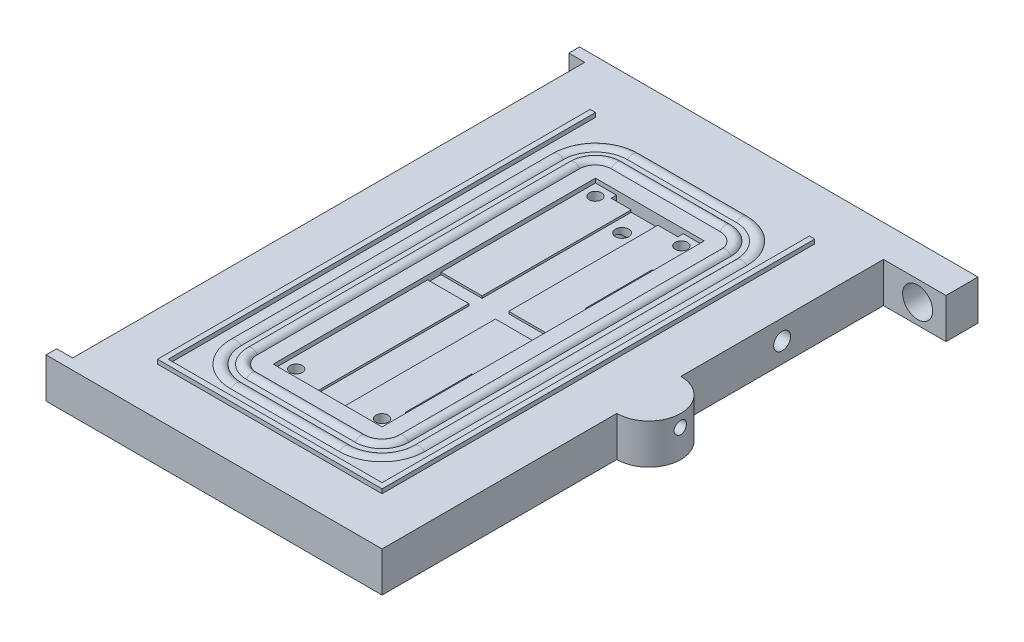
SolidWorks part; units mm, degrees
ref_plane "Front Plane" through (0, 0, 0) normal (0, 0, 1) x (1, 0, 0)
ref_plane "Top Plane" through (0, 0, 0) normal (0, 1, 0) x (1, 0, 0)
ref_plane "Right Plane" through (0, 0, 0) normal (1, 0, 0) x (0, 0, -1)
sketch "Sketch1" plane through (0, 0, 0) normal (0, 1, 0) x (1, 0, 0)
  line L12 (71.4455, 53.0596) -> (71.4455, -73.9404)
  line L13 (71.4455, -73.9404) -> (147.6455, -73.9404)
  line L14 (147.6455, -73.9404) -> (147.6455, 53.0596)
  line L15 (147.6455, 53.0596) -> (71.4455, 53.0596)
  dimension "D1" = 76.2
  dimension "D2" = 127
extrude "main body" add sketch "Sketch1" along normal blind 9.525
sketch "Sketch2" plane through (0, 9.525, 0) normal (0, 1, 0) x (1, 0, 0)
  line L0 (109.5455, 53.0596) -> (109.5455, 24.7212) construction
  line L1 (147.6455, 53.0596) -> (71.4455, 53.0596) construction
  line L2 (71.4455, -10.4404) -> (118.1145, -10.4404) construction
  line L3 (71.4455, 53.0596) -> (71.4455, -73.9404) construction
  line L4 (122.4995, -48.7944) -> (96.5915, -48.7944)
  line L5 (96.5915, -48.7944) -> (96.5915, 27.9136)
  line L6 (122.4995, -48.7944) -> (122.4995, 27.9136)
  line L7 (122.4995, 27.9136) -> (96.5915, 27.9136)
  line L8 (96.5915, 27.9136) -> (122.4995, -48.7944) construction
  point P11 (109.5455, 27.9136)
  point P13 (109.5455, -48.7944)
  point P14 (122.4995, -10.4404)
  point P15 (96.5915, -10.4404)
  dimension "D1" = 25.908
  dimension "D2" = 76.708
extrude "slide inset" cut sketch "Sketch2" against normal blind 1.016
ref_point "Point2 center of slide"
sketch "offset rounded from slide" plane through (0, 9.525, 0) normal (0, 1, 0) x (1, 0, 0)
  line L8 (125.0395, -51.3344) -> (125.0395, 30.4536)
  line L9 (94.0515, -51.3344) -> (125.0395, -51.3344)
  line L10 (94.0515, 30.4536) -> (94.0515, -51.3344)
  line L11 (125.0395, 30.4536) -> (94.0515, 30.4536)
  line L12 (125.0395, -48.7944) -> (125.0395, 27.9136)
  line L13 (96.5915, -51.3344) -> (122.4995, -51.3344)
  line L14 (94.0515, 27.9136) -> (94.0515, -48.7944)
  line L15 (122.4995, 30.4536) -> (96.5915, 30.4536)
  arc A0 (96.5915, -51.3344) -> (94.0515, -48.7944) centre (96.5915, -48.7944) cw
  arc A1 (125.0395, -48.7944) -> (122.4995, -51.3344) centre (122.4995, -48.7944) cw
  arc A2 (125.0395, 27.9136) -> (122.4995, 30.4536) centre (122.4995, 27.9136) ccw
  arc A3 (94.0515, 27.9136) -> (96.5915, 30.4536) centre (96.5915, 27.9136) cw
  dimension "D2" = 2.54
  dimension "D1" = 2.54
sketch "gasket bump profiles" plane through (0, 9.525, 0) normal (0, 1, 0) x (1, 0, 0)
  line L8 (91.5115, 27.9136) -> (91.5115, -48.7944)
  line L9 (96.5915, -53.8744) -> (122.4995, -53.8744)
  line L10 (127.5795, -48.7944) -> (127.5795, 27.9136)
  line L11 (122.4995, 32.9936) -> (96.5915, 32.9936)
  line L12 (91.5115, 27.9136) -> (91.5115, -48.7944)
  line L13 (96.5915, -53.8744) -> (122.4995, -53.8744)
  line L14 (127.5795, -48.7944) -> (127.5795, 27.9136)
  line L15 (122.4995, 32.9936) -> (96.5915, 32.9936)
  arc A8 (91.5115, -48.7944) -> (96.5915, -53.8744) centre (96.5915, -48.7944) ccw
  arc A9 (122.4995, -53.8744) -> (127.5795, -48.7944) centre (122.4995, -48.7944) ccw
  arc A10 (127.5795, 27.9136) -> (122.4995, 32.9936) centre (122.4995, 27.9136) ccw
  arc A11 (96.5915, 32.9936) -> (91.5115, 27.9136) centre (96.5915, 27.9136) ccw
  arc A16 (91.5115, -48.7944) -> (96.5915, -53.8744) centre (96.5915, -48.7944) ccw
  arc A17 (122.4995, -53.8744) -> (127.5795, -48.7944) centre (122.4995, -48.7944) ccw
  arc A18 (127.5795, 27.9136) -> (122.4995, 32.9936) centre (122.4995, 27.9136) ccw
  arc A19 (96.5915, 32.9936) -> (91.5115, 27.9136) centre (96.5915, 27.9136) ccw
  dimension "D1" = 2.54
ref_plane "Plane1 for gasket bump shape" through (0, 0, 10.4404) normal (0, 0, -1) x (-1, 0, 0)
sketch "gasket bump shape" plane through (0, 0, 10.4404) normal (0, 0, -1) x (-1, 0, 0)
  line L0 (-91.5115, 9.525) -> (-91.5115, 13.8205) construction
  line L1 (-90.2415, 9.525) -> (-92.7815, 9.525)
  line L2 (-91.5115, 10.3188) -> (-89.9155, 10.3187) construction
  line L3 (-91.5115, 9.525) -> (-87.7015, 9.525) construction
  line L4 (-89.6065, 9.525) -> (-89.6065, 13.8205) construction
  line L5 (-88.9715, 9.525) -> (-86.4315, 9.525)
  line L6 (-87.7015, 10.033) -> (-81.1283, 10.033) construction
  line L8 (-147.6455, 9.525) -> (-71.4455, 9.525) construction
  arc A0 (-90.2415, 9.525) -> (-92.7815, 9.525) centre (-91.5115, 8.9059) ccw
  arc A1 (-88.9715, 9.525) -> (-86.4315, 9.525) centre (-87.7015, 8.1915) cw
  dimension "D1" = 0.7937
  dimension "D2" = 2.54
  dimension "D3" = 3.81
  dimension "D4" = 0.508
sweep "Sweep for sealing ribs" add profiles "gasket bump shape" path "gasket bump profiles"
ref_plane "LR plane" through (0, 0, 10.4404) normal (0, 0, 1) x (1, 0, 0)
sketch "Sketch13" plane through (0, 9.525, 0) normal (0, 1, 0) x (1, 0, 0)
  line L3 (147.6455, -73.9404) -> (147.6455, 53.0596) construction
  line L4 (147.6455, -2.8204) -> (147.6455, -18.0604)
  arc A1 (147.6455, -2.8204) -> (147.6455, -18.0604) centre (147.6455, -10.4404) cw
  dimension "D2" = 7.62
extrude "bump for lid screw" add sketch "Sketch13" against normal up to surface (9.525 mm away) up to face at (109.5455, 0, 10.4404)
ref_plane "Plane2 front to back center plane" through (109.5455, 0, 0) normal (1, 0, 0) x (0, 0, -1)
hole_wizard "Tap Drill for #10-32 Tap1" positions "Sketch7" profile "Sketch6" hole size "#10-32" standard "Ansi Inch"
sketch "Sketch7" plane through (147.6455, 0, 0) normal (1, 0, 0) x (0, 0, -1)
  line L3 (-10.4404, 4.7625) -> (53.0596, 4.7625) construction
  line L6 (53.0596, 9.525) -> (53.0596, 0) construction
  line L7 (-10.4404, -5.2387) -> (-10.4404, 5.2387) construction
  point P0 (21.3096, 4.7625)
sketch "Sketch6" plane through (147.6455, 4.7625, -21.3096) normal (0, 1, 0) x (0, 0, -1)
  line L0 (0, 0) -> (0, 52.0133)
  line L1 (0, 52.0133) -> (2.0193, 50.8)
  line L2 (2.0193, 50.8) -> (2.0193, 0)
  line L5 (2.0193, 0) -> (0, 0)
  line L10 (0, 52.0133) -> (-2.0193, 50.8) construction
  line L11 (0, -6.35) -> (0, 107.95) construction
  dimension "Hole Dia." = 4.0386
  dimension "Hole Depth" = 50.8
  dimension "Drill Angle" = 118
hole_wizard "1/8 (0.125) Diameter Hole1" positions "Sketch9" profile "Sketch8" hole size "1/8" standard "Ansi Inch" end condition up to next
sketch "Sketch9" plane through (0, 8.509, 0) normal (0, 1, 0) x (-1, 0, 0)
  line L4 (-109.5455, 48.7944) -> (-109.5455, -27.9136) construction
  line L5 (-96.5915, 48.7944) -> (-122.4995, 48.7944) construction
  line L6 (-122.4995, -27.9136) -> (-96.5915, -27.9136) construction
  line L8 (-95.6322, -21.3096) -> (-143.5147, -21.3096) construction
  point P0 (-109.5455, -21.3096)
sketch "Sketch8" plane through (109.5455, 8.509, -21.3096) normal (1, 0, 0) x (0, 0, 1)
  line L0 (0, 0) -> (0, 1.7272)
  line L1 (0, 1.7272) -> (1.5875, 1.7272)
  line L2 (1.5875, 1.7272) -> (1.5875, 0)
  line L5 (1.5875, 0) -> (0, 0)
  line L11 (0, -6.35) -> (0, 107.95) construction
  dimension "Thru Hole Dia." = 3.175
  dimension "Thru Hole Depth" = 1.7272
sketch "Sketch24" plane through (0, 8.509, 0) normal (0, 1, 0) x (1, 0, 0)
  line L0 (109.5455, -48.7944) -> (109.5455, 27.9136) construction
  line L1 (96.5915, -48.7944) -> (122.4995, -48.7944) construction
  line L2 (122.4995, 27.9136) -> (96.5915, 27.9136) construction
  line L3 (109.5455, -10.4404) -> (80.3717, -10.4404) construction
  line L4 (112.7205, 27.9136) -> (106.3705, 27.9136)
  line L5 (106.3705, 27.9136) -> (106.3705, -8.8529)
  line L6 (106.3705, -8.8529) -> (96.5915, -8.8529)
  line L7 (96.5915, -8.8529) -> (96.5915, -12.0279)
  line L8 (122.4995, -8.8529) -> (122.4995, -12.0279)
  line L9 (112.7205, -8.8529) -> (122.4995, -8.8529)
  line L10 (112.7205, 27.9136) -> (112.7205, -8.8529)
  line L11 (112.7205, -48.7944) -> (112.7205, -12.0279)
  line L12 (112.7205, -12.0279) -> (122.4995, -12.0279)
  line L13 (106.3705, -12.0279) -> (96.5915, -12.0279)
  line L14 (106.3705, -48.7944) -> (106.3705, -12.0279)
  line L15 (112.7205, -48.7944) -> (106.3705, -48.7944)
  line L16 (96.5915, 27.9136) -> (96.5915, -48.7944) construction
  line L17 (122.4995, 27.9136) -> (96.5915, 27.9136) construction
  point P17 (109.5455, 27.9136)
  point P20 (122.4995, -10.4404)
  point P21 (96.5915, -10.4404)
  point P23 (109.5455, -48.7944)
  dimension "D1" = 6.35
  dimension "D2" = 3.175
extrude "Cut-Extrude8" cut sketch "Sketch24" against normal blind 0.508
ref_axis "Axis1 perp to slide at center" through (109.5455, 8.509, 10.4404) along (0, 1, 0)
sketch "Sketch25" plane through (0, 0, -53.0596) normal (0, 0, -1) x (-1, 0, 0)
  line L0 (-147.6455, 9.525) -> (-71.4455, 9.525) construction
  line L1 (-147.6455, 9.525) -> (-162.5204, 9.525)
  line L2 (-147.6455, 9.525) -> (-147.6455, 0)
  line L3 (-147.6455, 0) -> (-162.5204, 0)
  line L4 (-162.5204, 9.525) -> (-162.5204, 0)
  line L5 (-147.6455, 0) -> (-71.4455, 0) construction
  line L6 (-162.5204, 4.7625) -> (-147.6455, 4.7625) construction
  line L7 (-159.3454, 4.7625) -> (-159.3454, 16.781) construction
  circle A0 centre (-155.7735, 4.7625) radius 3.5719
  dimension "D1" = 7.1437
  dimension "D2" = 8.128
  dimension "D3" = 3.175
extrude "vacuum hose strain relief" add sketch "Sketch25" against normal blind 7.62
sketch "Sketch31" plane through (0, 0, 73.9404) normal (0, 0, 1) x (1, 0, 0)
  line L0 (71.4455, 4.7625) -> (99.2275, 4.7625) construction
  line L1 (71.4455, 9.525) -> (71.4455, 0) construction
  line L2 (71.4455, 7.1438) -> (71.4455, 2.3813)
  arc A0 (71.4455, 7.1438) -> (71.4455, 2.3813) centre (71.4455, 4.7625) cw
  dimension "D1" = 2.3813
extrude "hinge" cut sketch "Sketch31" against normal up to surface (127 mm away) up to face at (116.983, 4.7625, -53.0596)
sketch "Sketch32" plane through (147.6455, 0, 0) normal (1, 0, 0) x (0, 0, -1)
  line L0 (-10.4404, 9.525) -> (-10.4404, 0) construction
  line L4 (-18.0604, 0) -> (-2.8204, 0) construction
  line L5 (-2.8204, 9.525) -> (-18.0604, 9.525) construction
  circle A0 centre (-10.4404, 6.6137) radius 1.4732
  dimension "D1" = 2.9464
extrude "hole for screw latch" cut sketch "Sketch32" along normal through all
sketch "Sketch33" plane through (71.4455, 0, 0) normal (-1, 0, 0) x (0, 0, 1)
  line L0 (10.4404, 0) -> (10.4404, 9.525) construction
  line L1 (-38.5181, 0) -> (59.3989, 0) construction
  line L2 (-53.0596, 9.525) -> (73.9404, 9.525) construction
  line L3 (-50.5196, 0) -> (-50.5196, 9.525)
  line L4 (73.9404, 0) -> (71.4004, 0)
  line L5 (73.9404, 0) -> (73.9404, 9.525)
  line L6 (73.9404, 9.525) -> (71.4004, 9.525)
  line L7 (71.4004, 0) -> (71.4004, 9.525)
  line L8 (-53.0596, 9.525) -> (-50.5196, 9.525)
  line L9 (-53.0596, 0) -> (-53.0596, 9.525)
  line L10 (-53.0596, 0) -> (-50.5196, 0)
  dimension "D1" = 2.54
extrude "hinge centering tabs" add sketch "Sketch33" along normal mid plane 7.62
sketch "Sketch35" plane through (0, 9.525, 0) normal (0, 1, 0) x (1, 0, 0)
  line L0 (109.5455, 27.9136) -> (109.5455, -48.7944) construction
  line L1 (122.4995, 27.9136) -> (96.5915, 27.9136) construction
  line L2 (96.5915, -48.7944) -> (122.4995, -48.7944) construction
  line L3 (135.009, -61.3039) -> (84.082, -61.3039)
  line L4 (96.5915, 27.9136) -> (96.5915, -48.7944) construction
  line L5 (96.5915, -10.4404) -> (122.4995, -10.4404) construction
  line L6 (122.4995, -48.7944) -> (122.4995, 27.9136) construction
  line L7 (84.082, -61.3039) -> (84.082, 40.4231)
  line L8 (86.4315, 27.9136) -> (86.4315, -48.7944) construction
  line L10 (122.4995, -58.9544) -> (96.5915, -58.9544) construction
  line L11 (136.279, -62.5739) -> (136.279, 40.4231)
  line L12 (135.009, -61.3039) -> (135.009, 40.4231)
  line L13 (136.279, -62.5739) -> (82.812, -62.5739)
  line L14 (82.812, -62.5739) -> (82.812, 40.4231)
  line L15 (82.812, 40.4231) -> (84.082, 40.4231)
  line L16 (135.009, 40.4231) -> (136.279, 40.4231)
  point P20 (84.082, -10.4404)
  point P21 (135.009, -10.4404)
  point P23 (109.5455, 40.4231)
  point P24 (109.5455, -61.3039)
  dimension "D1" = 50.927
  dimension "D2" = 2.3495
  dimension "D3" = 2.3495
  dimension "D4" = 1.27
extrude "tape fence" add sketch "Sketch35" along normal blind 1.016
sketch "Sketch36" plane through (0, 8.509, 0) normal (0, 1, 0) x (1, 0, 0)
  line L1 (96.5915, 27.9136) -> (96.5915, -48.7944) construction
  line L2 (122.4995, 27.9136) -> (96.5915, 27.9136) construction
  circle A0 centre (99.322, 25.1831) radius 1.4605
  dimension "D1" = 2.921
  dimension "D2" = 1.27
  dimension "D3" = 1.27
extrude "Cut-Extrude9" cut sketch "Sketch36" against normal blind 6.604
mirror "Mirror1" about plane through (0, 0, 10.4404) normal (0, 0, 1) of "Cut-Extrude9"
mirror "Mirror2" about plane through (109.5455, 0, 0) normal (1, 0, 0) of "Mirror1"
sketch "Sketch37" plane through (0, 8.509, 0) normal (0, 1, 0) x (1, 0, 0)
  line L0 (96.5915, -10.4404) -> (122.4995, -10.4404) construction
  line L1 (96.5915, 27.9136) -> (96.5915, -48.7944) construction
  line L2 (122.4995, -48.7944) -> (122.4995, 27.9136) construction
  line L3 (109.5455, 27.9136) -> (109.5455, -48.7944) construction
  line L4 (122.4995, 27.9136) -> (96.5915, 27.9136) construction
  line L5 (96.5915, -48.7944) -> (122.4995, -48.7944) construction
  line L6 (121.2295, 16.7503) -> (121.2295, 0.8753)
  line L7 (122.4995, -42.0634) -> (121.2295, -42.0634)
  line L8 (122.4995, -42.0634) -> (122.4995, -26.1884)
  line L9 (122.4995, -26.1884) -> (121.2295, -26.1884)
  line L10 (121.2295, -42.0634) -> (121.2295, -26.1884)
  line L11 (122.4995, 0.8753) -> (121.2295, 0.8753)
  line L12 (122.4995, 16.7503) -> (122.4995, 0.8753)
  line L13 (122.4995, 16.7503) -> (121.2295, 16.7503)
  line L14 (101.608, 27.9136) -> (117.483, 27.9136)
  line L15 (101.608, 26.6436) -> (117.483, 26.6436)
  line L16 (101.608, 27.9136) -> (101.608, 26.6436)
  line L17 (117.483, 27.9136) -> (117.483, 26.6436)
  line L18 (96.8455, 19.2903) -> (147.6455, 19.2903) construction
  circle A0 centre (119.769, -46.0639) radius 1.4605 construction
  dimension "D1" = 15.875
  dimension "D2" = 1.27
  dimension "D3" = 2.54
  dimension "D4" = 1.27
  dimension "D5" = 15.875
  dimension "D6" = 1.27
  dimension "D7" = 15.875
  dimension "D8" = 2.54
extrude "Cut-Extrude10" cut sketch "Sketch37" against normal blind 5.08
equation "\"D3@Sketch35\" = \"D2@Sketch35\""
